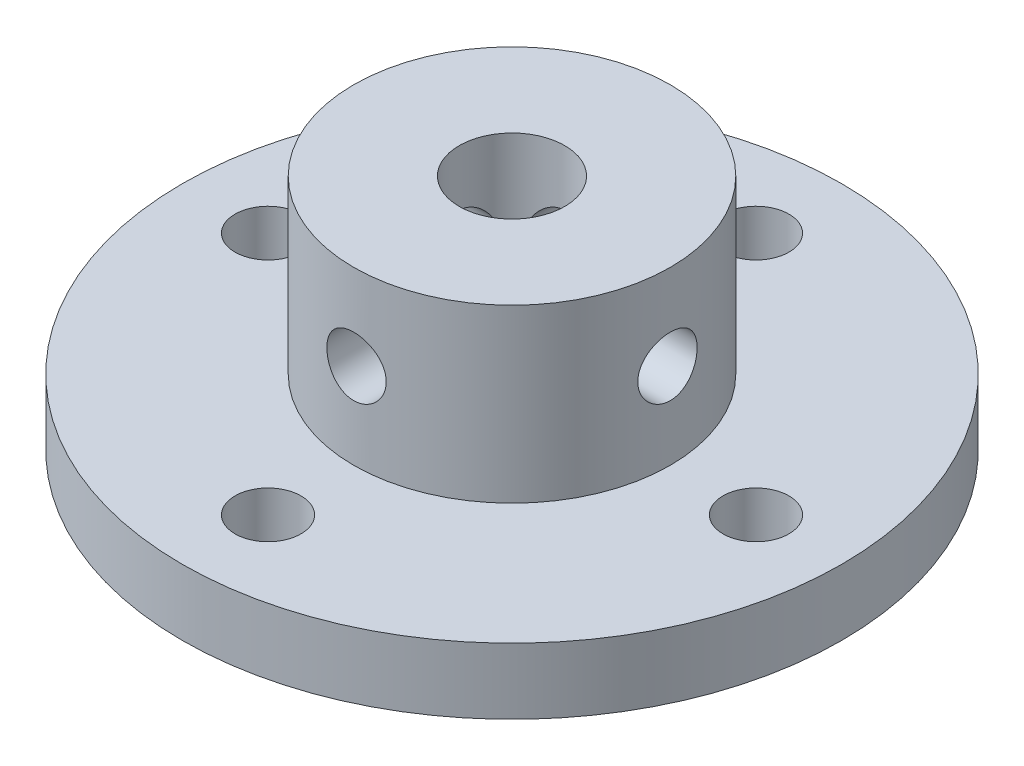
SolidWorks part; units mm, degrees
ref_plane "前视基准面" through (0, 0, 0) normal (0, 0, 1) x (1, 0, 0)
ref_plane "上视基准面" through (0, 0, 0) normal (0, 1, 0) x (1, 0, 0)
ref_plane "右视基准面" through (0, 0, 0) normal (1, 0, 0) x (0, 0, -1)
other "Configuration Table"
sketch "草图1" plane through (0, 0, 0) normal (0, 1, 0) x (1, 0, 0)
  circle A0 centre (0, 0) radius 25
  dimension "D1" = 50
extrude "凸台-拉伸1" add sketch "草图1" along normal blind 5
sketch "草图2" plane through (0, 5, 0) normal (0, 1, 0) x (1, 0, 0)
  circle A0 centre (0, 0) radius 12
  dimension "D1" = 24
extrude "凸台-拉伸2" add sketch "草图2" along normal blind 13
sketch "草图3" plane through (0, 18, 0) normal (0, 1, 0) x (1, 0, 0)
  circle A0 centre (0, 0) radius 4
  dimension "D1" = 8
extrude "切除-拉伸1" cut sketch "草图3" against normal through all
sketch "草图4" plane through (0, 5, 0) normal (0, 1, 0) x (1, 0, 0)
  circle A0 centre (0, 0) radius 18.5
  circle A1 centre (0, 18.5) radius 2.5
  circle A2 centre (18.5, 0) radius 2.5
  circle A3 centre (0, -18.5) radius 2.5
  circle A4 centre (-18.5, 0) radius 2.5
  dimension "D1" = 37
  dimension "D2" = 5
  dimension "D3" = 5
  dimension "D4" = 5
  dimension "D5" = 5
extrude "切除-拉伸2" cut sketch "草图4" against normal through all contours A0 A1 | A0 A1 | A0 A2 | A0 A2 | A0 A3 | A0 A3 | A0 A4 | A0 A4 region at (17.4091, 5, 0) region at (19.53, 5, 0) region at (0, 5, -17.4091) region at (0, 5, -19.53) region at (0, 5, 19.53) region at (0, 5, 17.4091) region at (-17.4091, 5, 0) region at (-19.53, 5, 0)
sketch "草图5" plane through (0, 0, 0) normal (1, 0, 0) x (0, 0, -1)
  line L0 (0, 9.9) -> (0, -9.9) construction
  line L1 (12, 18) -> (-12, 18) construction
  circle A0 centre (0, 11.5) radius 2.25
  dimension "D1" = 4.5
  dimension "D2" = 6.5
extrude "切除-拉伸3" cut sketch "草图5" against normal through all and the other way through all
cosmetic thread "装饰螺纹线2" parameters "D2"=5.5
cosmetic thread "装饰螺纹线4" parameters "D2"=5.5
sketch "草图6" plane through (0, 0, 0) normal (0, 0, 1) x (1, 0, 0)
  line L0 (0, -9.9) -> (0, 9.9) construction
  line L1 (4, 18) -> (-4, 18) construction
  circle A0 centre (0, 11.5) radius 2.25
  dimension "D1" = 4.5
  dimension "D2" = 6.5
extrude "切除-拉伸4" cut sketch "草图6" against normal through all and the other way through all
cosmetic thread "装饰螺纹线1" parameters "D2"=5.5
cosmetic thread "装饰螺纹线3" parameters "D2"=5.5
